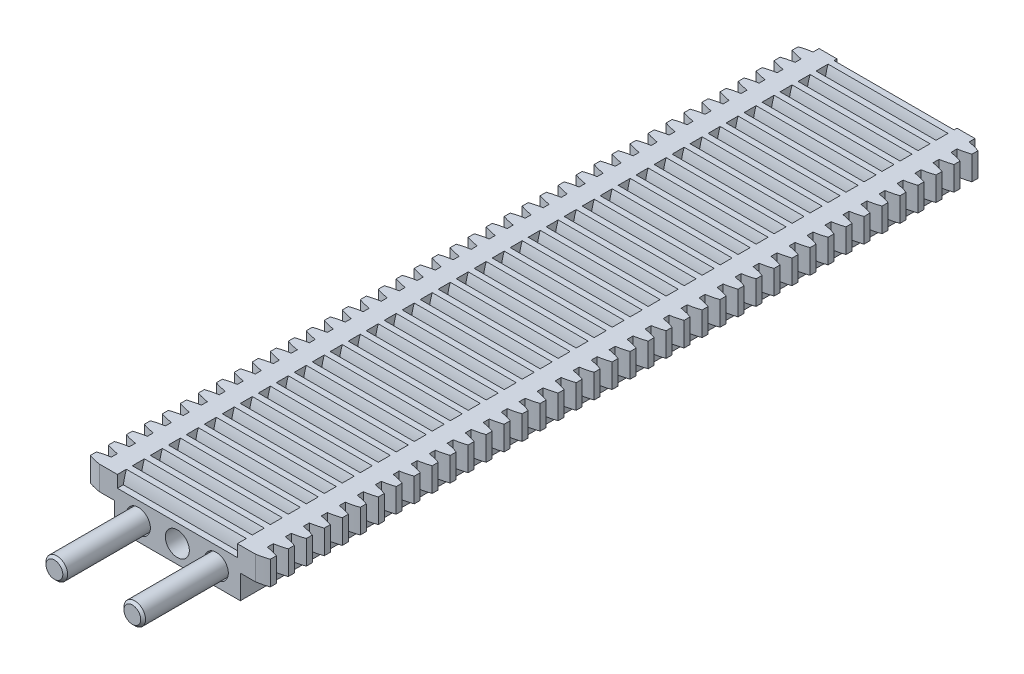
SolidWorks part; units mm, degrees
ref_plane "前视基准面" through (0, 0, 0) normal (0, 0, 1) x (1, 0, 0)
ref_plane "上视基准面" through (0, 0, 0) normal (0, 1, 0) x (1, 0, 0)
ref_plane "右视基准面" through (0, 0, 0) normal (1, 0, 0) x (0, 0, -1)
sketch "草图1" plane through (0, 0, 0) normal (0, 0, 1) x (1, 0, 0)
  line L0 (5.25, 2) -> (6.5, 2)
  line L1 (-5.25, 0) -> (5.25, 0)
  line L2 (-5.25, 0) -> (-5.25, 2)
  line L4 (5.25, 0) -> (5.25, 2)
  line L5 (-6.5, 2) -> (-5.25, 2)
  line L6 (-6.5, 2) -> (-6.5, 4)
  line L7 (-6.5, 4) -> (6.5, 4)
  line L8 (6.5, 2) -> (6.5, 4)
extrude "凸台-拉伸1" add sketch "草图1" against normal blind 60
sketch "草图2" plane through (0, 0, 0) normal (0, 0, 1) x (1, 0, 0)
  line L0 (-1.95, -2.5) -> (-1.1658, -2.5)
  line L1 (-1.95, -2.5) -> (-1.95, -1.5556)
  line L2 (-5.25, 0) -> (5.25, 0) construction
  line L3 (1.95, -2.5) -> (1.95, -1.5556)
  line L4 (0, 0) -> (-1.1658, -2.5)
  line L5 (-1.5, 0) -> (0, 0)
  line L6 (-1.5, 0) -> (-1.5, -0.6771)
  line L7 (0, 0) -> (1.1658, -2.5)
  line L8 (1.5, 0) -> (1.5, -0.6771)
  line L9 (1.1658, -2.5) -> (1.95, -2.5)
  line L10 (0, 0) -> (1.5, 0)
  arc A0 (-1.5, -0.6771) -> (-1.95, -1.5556) centre (0, -2) ccw
  arc A2 (1.95, -1.5556) -> (1.5, -0.6771) centre (0, -2) ccw
  line M2 (-5.25, 0) -> (5.25, 0)
extrude "凸台-拉伸2" add sketch "草图2" against normal blind 54 from offset 3 contours L6 A0 L1 L0 L4 M2 | L3 A2 L8 L7 L9 M2 region at (-1.1423, -1.1553, 0) region at (1.1423, -1.1553, 0) offset against normal yes
sketch "草图3" plane through (0, 0, 0) normal (0, 0, 1) x (1, 0, 0)
  circle A0 centre (-3.25, 1.5) radius 1
  circle A1 centre (0, 1.5) radius 1
  circle A2 centre (3.25, 1.5) radius 1
extrude "切除-拉伸1" cut sketch "草图3" against normal through all
sketch "草图4" plane through (0, 0, 0) normal (0, 0, 1) x (1, 0, 0)
  circle A0 centre (-3.25, 1.5) radius 0.9
  circle A1 centre (3.25, 1.5) radius 0.9
extrude "凸台-拉伸3" add sketch "草图4" along normal blind 7 and the other way blind 7 separate body
fillet "圆角1" radius 0.1 8 edges at (-1.1658, -2.5, -30) (-1.5579, -2.5, -57) (-1.95, -2.5, -30) (-1.5579, -2.5, -3) (1.95, -2.5, -30) (1.5579, -2.5, -57) (1.1658, -2.5, -30) (1.5579, -2.5, -3)
chamfer "倒角2" distance 0.2 angle 45 1 edges at (-2.35, 1.5, 7)
chamfer "倒角3" distance 0.2 angle 45 1 edges at (4.15, 1.5, 7)
sketch "草图6" plane through (0, 4, 0) normal (0, 1, 0) x (1, 0, 0)
  line L0 (-6.5, 59.5) -> (-6.5, 58.5)
  line L1 (-6.5, 60) -> (-6.5, 0) construction
  line L2 (-6.5, 58) -> (-6.5, 57)
  line L3 (-7.5, 59.25) -> (-7.5, 58.75)
  line L4 (-7.5, 57.75) -> (-7.5, 57.25)
  line L5 (-7.5, 56.25) -> (-7.5, 55.75)
  line L6 (-6.5, 56.5) -> (-6.5, 55.5)
  line L7 (-7.5, 54.75) -> (-7.5, 54.25)
  line L8 (-6.5, 55) -> (-6.5, 54)
  line L9 (-7.5, 53.25) -> (-7.5, 52.75)
  line L10 (-6.5, 53.5) -> (-6.5, 52.5)
  line L11 (-7.5, 51.75) -> (-7.5, 51.25)
  line L12 (-6.5, 52) -> (-6.5, 51)
  line L13 (-7.5, 50.25) -> (-7.5, 49.75)
  line L14 (-6.5, 50.5) -> (-6.5, 49.5)
  line L15 (-7.5, 48.75) -> (-7.5, 48.25)
  line L16 (-6.5, 49) -> (-6.5, 48)
  line L17 (-7.5, 47.25) -> (-7.5, 46.75)
  line L18 (-6.5, 47.5) -> (-6.5, 46.5)
  line L19 (-7.5, 45.75) -> (-7.5, 45.25)
  line L20 (-6.5, 46) -> (-6.5, 45)
  line L21 (-7.5, 44.25) -> (-7.5, 43.75)
  line L22 (-6.5, 44.5) -> (-6.5, 43.5)
  line L23 (-7.5, 42.75) -> (-7.5, 42.25)
  line L24 (-6.5, 43) -> (-6.5, 42)
  line L25 (-7.5, 41.25) -> (-7.5, 40.75)
  line L26 (-6.5, 41.5) -> (-6.5, 40.5)
  line L27 (-7.5, 39.75) -> (-7.5, 39.25)
  line L28 (-6.5, 40) -> (-6.5, 39)
  line L29 (-7.5, 38.25) -> (-7.5, 37.75)
  line L30 (-6.5, 38.5) -> (-6.5, 37.5)
  line L31 (-7.5, 36.75) -> (-7.5, 36.25)
  line L32 (-6.5, 37) -> (-6.5, 36)
  line L33 (-7.5, 35.25) -> (-7.5, 34.75)
  line L34 (-6.5, 35.5) -> (-6.5, 34.5)
  line L35 (-7.5, 33.75) -> (-7.5, 33.25)
  line L36 (-6.5, 34) -> (-6.5, 33)
  line L37 (-7.5, 32.25) -> (-7.5, 31.75)
  line L38 (-6.5, 32.5) -> (-6.5, 31.5)
  line L39 (-7.5, 30.75) -> (-7.5, 30.25)
  line L40 (-6.5, 31) -> (-6.5, 30)
  line L41 (-7.5, 29.25) -> (-7.5, 28.75)
  line L42 (-6.5, 29.5) -> (-6.5, 28.5)
  line L43 (-7.5, 27.75) -> (-7.5, 27.25)
  line L44 (-6.5, 28) -> (-6.5, 27)
  line L45 (-7.5, 26.25) -> (-7.5, 25.75)
  line L46 (-6.5, 26.5) -> (-6.5, 25.5)
  line L47 (-7.5, 24.75) -> (-7.5, 24.25)
  line L48 (-6.5, 25) -> (-6.5, 24)
  line L49 (-7.5, 23.25) -> (-7.5, 22.75)
  line L50 (-6.5, 23.5) -> (-6.5, 22.5)
  line L51 (-7.5, 21.75) -> (-7.5, 21.25)
  line L52 (-6.5, 22) -> (-6.5, 21)
  line L53 (-7.5, 20.25) -> (-7.5, 19.75)
  line L54 (-6.5, 20.5) -> (-6.5, 19.5)
  line L55 (-7.5, 18.75) -> (-7.5, 18.25)
  line L56 (-6.5, 19) -> (-6.5, 18)
  line L57 (-7.5, 17.25) -> (-7.5, 16.75)
  line L58 (-6.5, 17.5) -> (-6.5, 16.5)
  line L59 (-7.5, 15.75) -> (-7.5, 15.25)
  line L60 (-6.5, 16) -> (-6.5, 15)
  line L61 (-7.5, 14.25) -> (-7.5, 13.75)
  line L62 (-6.5, 14.5) -> (-6.5, 13.5)
  line L63 (-7.5, 12.75) -> (-7.5, 12.25)
  line L64 (-6.5, 13) -> (-6.5, 12)
  line L65 (-7.5, 11.25) -> (-7.5, 10.75)
  line L66 (-6.5, 11.5) -> (-6.5, 10.5)
  line L67 (-7.5, 9.75) -> (-7.5, 9.25)
  line L68 (-6.5, 10) -> (-6.5, 9)
  line L69 (-7.5, 8.25) -> (-7.5, 7.75)
  line L70 (-6.5, 8.5) -> (-6.5, 7.5)
  line L71 (-7.5, 6.75) -> (-7.5, 6.25)
  line L72 (-6.5, 7) -> (-6.5, 6)
  line L73 (-7.5, 5.25) -> (-7.5, 4.75)
  line L74 (-6.5, 5.5) -> (-6.5, 4.5)
  line L75 (-7.5, 3.75) -> (-7.5, 3.25)
  line L76 (-6.5, 4) -> (-6.5, 3)
  line L77 (-7.5, 2.25) -> (-7.5, 1.75)
  line L78 (-6.5, 2.5) -> (-6.5, 1.5)
  line L79 (-6.5, 1) -> (-6.5, 0)
  line L80 (-7.5, 0.75) -> (-7.5, 0.25)
  line L81 (0, 62.425) -> (0, -2.925) construction
  line L82 (7.5, 0.75) -> (7.5, 0.25)
  line L83 (6.5, 1) -> (6.5, 0)
  line L84 (6.5, 2.5) -> (6.5, 1.5)
  line L85 (7.5, 2.25) -> (7.5, 1.75)
  line L86 (6.5, 4) -> (6.5, 3)
  line L87 (7.5, 3.75) -> (7.5, 3.25)
  line L88 (6.5, 5.5) -> (6.5, 4.5)
  line L89 (7.5, 5.25) -> (7.5, 4.75)
  line L90 (6.5, 7) -> (6.5, 6)
  line L91 (7.5, 6.75) -> (7.5, 6.25)
  line L92 (6.5, 8.5) -> (6.5, 7.5)
  line L93 (7.5, 8.25) -> (7.5, 7.75)
  line L94 (6.5, 10) -> (6.5, 9)
  line L95 (7.5, 9.75) -> (7.5, 9.25)
  line L96 (6.5, 11.5) -> (6.5, 10.5)
  line L97 (7.5, 11.25) -> (7.5, 10.75)
  line L98 (6.5, 13) -> (6.5, 12)
  line L99 (7.5, 12.75) -> (7.5, 12.25)
  line L100 (6.5, 14.5) -> (6.5, 13.5)
  line L101 (7.5, 14.25) -> (7.5, 13.75)
  line L102 (6.5, 16) -> (6.5, 15)
  line L103 (7.5, 15.75) -> (7.5, 15.25)
  line L104 (6.5, 17.5) -> (6.5, 16.5)
  line L105 (7.5, 17.25) -> (7.5, 16.75)
  line L106 (6.5, 19) -> (6.5, 18)
  line L107 (7.5, 18.75) -> (7.5, 18.25)
  line L108 (6.5, 20.5) -> (6.5, 19.5)
  line L109 (7.5, 20.25) -> (7.5, 19.75)
  line L110 (6.5, 22) -> (6.5, 21)
  line L111 (7.5, 21.75) -> (7.5, 21.25)
  line L112 (6.5, 23.5) -> (6.5, 22.5)
  line L113 (7.5, 23.25) -> (7.5, 22.75)
  line L114 (6.5, 25) -> (6.5, 24)
  line L115 (7.5, 24.75) -> (7.5, 24.25)
  line L116 (6.5, 26.5) -> (6.5, 25.5)
  line L117 (7.5, 26.25) -> (7.5, 25.75)
  line L118 (6.5, 28) -> (6.5, 27)
  line L119 (7.5, 27.75) -> (7.5, 27.25)
  line L120 (6.5, 29.5) -> (6.5, 28.5)
  line L121 (7.5, 29.25) -> (7.5, 28.75)
  line L122 (6.5, 31) -> (6.5, 30)
  line L123 (7.5, 30.75) -> (7.5, 30.25)
  line L124 (6.5, 32.5) -> (6.5, 31.5)
  line L125 (7.5, 32.25) -> (7.5, 31.75)
  line L126 (6.5, 34) -> (6.5, 33)
  line L127 (7.5, 33.75) -> (7.5, 33.25)
  line L128 (6.5, 35.5) -> (6.5, 34.5)
  line L129 (7.5, 35.25) -> (7.5, 34.75)
  line L130 (6.5, 37) -> (6.5, 36)
  line L131 (7.5, 36.75) -> (7.5, 36.25)
  line L132 (6.5, 38.5) -> (6.5, 37.5)
  line L133 (7.5, 38.25) -> (7.5, 37.75)
  line L134 (6.5, 40) -> (6.5, 39)
  line L135 (7.5, 39.75) -> (7.5, 39.25)
  line L136 (6.5, 41.5) -> (6.5, 40.5)
  line L137 (7.5, 41.25) -> (7.5, 40.75)
  line L138 (6.5, 43) -> (6.5, 42)
  line L139 (7.5, 42.75) -> (7.5, 42.25)
  line L140 (6.5, 44.5) -> (6.5, 43.5)
  line L141 (7.5, 44.25) -> (7.5, 43.75)
  line L142 (6.5, 46) -> (6.5, 45)
  line L143 (7.5, 45.75) -> (7.5, 45.25)
  line L144 (6.5, 47.5) -> (6.5, 46.5)
  line L145 (7.5, 47.25) -> (7.5, 46.75)
  line L146 (6.5, 49) -> (6.5, 48)
  line L147 (7.5, 48.75) -> (7.5, 48.25)
  line L148 (6.5, 50.5) -> (6.5, 49.5)
  line L149 (7.5, 50.25) -> (7.5, 49.75)
  line L150 (6.5, 52) -> (6.5, 51)
  line L151 (7.5, 51.75) -> (7.5, 51.25)
  line L152 (6.5, 53.5) -> (6.5, 52.5)
  line L153 (7.5, 53.25) -> (7.5, 52.75)
  line L154 (6.5, 55) -> (6.5, 54)
  line L155 (7.5, 54.75) -> (7.5, 54.25)
  line L156 (6.5, 56.5) -> (6.5, 55.5)
  line L157 (7.5, 56.25) -> (7.5, 55.75)
  line L158 (7.5, 57.75) -> (7.5, 57.25)
  line L159 (7.5, 59.25) -> (7.5, 58.75)
  line L160 (6.5, 58) -> (6.5, 57)
  line L161 (6.5, 59.5) -> (6.5, 58.5)
  arc A0 (-7.5, 58.75) -> (-6.5, 58.5) centre (-5.675, 63.925) ccw
  arc A1 (-7.5, 59.25) -> (-6.5, 59.5) centre (-5.675, 54.075) cw
  arc A2 (-7.5, 57.25) -> (-6.5, 57) centre (-5.675, 62.425) ccw
  arc A3 (-7.5, 57.75) -> (-6.5, 58) centre (-5.675, 52.575) cw
  arc A4 (-7.5, 54.25) -> (-6.5, 54) centre (-5.675, 59.425) ccw
  arc A5 (-7.5, 56.25) -> (-6.5, 56.5) centre (-5.675, 51.075) cw
  arc A6 (-7.5, 54.75) -> (-6.5, 55) centre (-5.675, 49.575) cw
  arc A7 (-7.5, 55.75) -> (-6.5, 55.5) centre (-5.675, 60.925) ccw
  arc A8 (-7.5, 51.25) -> (-6.5, 51) centre (-5.675, 56.425) ccw
  arc A9 (-7.5, 53.25) -> (-6.5, 53.5) centre (-5.675, 48.075) cw
  arc A10 (-7.5, 51.75) -> (-6.5, 52) centre (-5.675, 46.575) cw
  arc A11 (-7.5, 52.75) -> (-6.5, 52.5) centre (-5.675, 57.925) ccw
  arc A12 (-7.5, 48.25) -> (-6.5, 48) centre (-5.675, 53.425) ccw
  arc A13 (-7.5, 50.25) -> (-6.5, 50.5) centre (-5.675, 45.075) cw
  arc A14 (-7.5, 48.75) -> (-6.5, 49) centre (-5.675, 43.575) cw
  arc A15 (-7.5, 49.75) -> (-6.5, 49.5) centre (-5.675, 54.925) ccw
  arc A16 (-7.5, 45.25) -> (-6.5, 45) centre (-5.675, 50.425) ccw
  arc A17 (-7.5, 47.25) -> (-6.5, 47.5) centre (-5.675, 42.075) cw
  arc A18 (-7.5, 45.75) -> (-6.5, 46) centre (-5.675, 40.575) cw
  arc A19 (-7.5, 46.75) -> (-6.5, 46.5) centre (-5.675, 51.925) ccw
  arc A20 (-7.5, 42.25) -> (-6.5, 42) centre (-5.675, 47.425) ccw
  arc A21 (-7.5, 44.25) -> (-6.5, 44.5) centre (-5.675, 39.075) cw
  arc A22 (-7.5, 42.75) -> (-6.5, 43) centre (-5.675, 37.575) cw
  arc A23 (-7.5, 43.75) -> (-6.5, 43.5) centre (-5.675, 48.925) ccw
  arc A24 (-7.5, 39.25) -> (-6.5, 39) centre (-5.675, 44.425) ccw
  arc A25 (-7.5, 41.25) -> (-6.5, 41.5) centre (-5.675, 36.075) cw
  arc A26 (-7.5, 39.75) -> (-6.5, 40) centre (-5.675, 34.575) cw
  arc A27 (-7.5, 40.75) -> (-6.5, 40.5) centre (-5.675, 45.925) ccw
  arc A28 (-7.5, 36.25) -> (-6.5, 36) centre (-5.675, 41.425) ccw
  arc A29 (-7.5, 38.25) -> (-6.5, 38.5) centre (-5.675, 33.075) cw
  arc A30 (-7.5, 36.75) -> (-6.5, 37) centre (-5.675, 31.575) cw
  arc A31 (-7.5, 37.75) -> (-6.5, 37.5) centre (-5.675, 42.925) ccw
  arc A32 (-7.5, 33.25) -> (-6.5, 33) centre (-5.675, 38.425) ccw
  arc A33 (-7.5, 35.25) -> (-6.5, 35.5) centre (-5.675, 30.075) cw
  arc A34 (-7.5, 33.75) -> (-6.5, 34) centre (-5.675, 28.575) cw
  arc A35 (-7.5, 34.75) -> (-6.5, 34.5) centre (-5.675, 39.925) ccw
  arc A36 (-7.5, 30.25) -> (-6.5, 30) centre (-5.675, 35.425) ccw
  arc A37 (-7.5, 32.25) -> (-6.5, 32.5) centre (-5.675, 27.075) cw
  arc A38 (-7.5, 30.75) -> (-6.5, 31) centre (-5.675, 25.575) cw
  arc A39 (-7.5, 31.75) -> (-6.5, 31.5) centre (-5.675, 36.925) ccw
  arc A40 (-7.5, 27.25) -> (-6.5, 27) centre (-5.675, 32.425) ccw
  arc A41 (-7.5, 29.25) -> (-6.5, 29.5) centre (-5.675, 24.075) cw
  arc A42 (-7.5, 27.75) -> (-6.5, 28) centre (-5.675, 22.575) cw
  arc A43 (-7.5, 28.75) -> (-6.5, 28.5) centre (-5.675, 33.925) ccw
  arc A44 (-7.5, 24.25) -> (-6.5, 24) centre (-5.675, 29.425) ccw
  arc A45 (-7.5, 26.25) -> (-6.5, 26.5) centre (-5.675, 21.075) cw
  arc A46 (-7.5, 24.75) -> (-6.5, 25) centre (-5.675, 19.575) cw
  arc A47 (-7.5, 25.75) -> (-6.5, 25.5) centre (-5.675, 30.925) ccw
  arc A48 (-7.5, 21.25) -> (-6.5, 21) centre (-5.675, 26.425) ccw
  arc A49 (-7.5, 23.25) -> (-6.5, 23.5) centre (-5.675, 18.075) cw
  arc A50 (-7.5, 21.75) -> (-6.5, 22) centre (-5.675, 16.575) cw
  arc A51 (-7.5, 22.75) -> (-6.5, 22.5) centre (-5.675, 27.925) ccw
  arc A52 (-7.5, 18.25) -> (-6.5, 18) centre (-5.675, 23.425) ccw
  arc A53 (-7.5, 20.25) -> (-6.5, 20.5) centre (-5.675, 15.075) cw
  arc A54 (-7.5, 18.75) -> (-6.5, 19) centre (-5.675, 13.575) cw
  arc A55 (-7.5, 19.75) -> (-6.5, 19.5) centre (-5.675, 24.925) ccw
  arc A56 (-7.5, 15.25) -> (-6.5, 15) centre (-5.675, 20.425) ccw
  arc A57 (-7.5, 17.25) -> (-6.5, 17.5) centre (-5.675, 12.075) cw
  arc A58 (-7.5, 15.75) -> (-6.5, 16) centre (-5.675, 10.575) cw
  arc A59 (-7.5, 16.75) -> (-6.5, 16.5) centre (-5.675, 21.925) ccw
  arc A60 (-7.5, 12.25) -> (-6.5, 12) centre (-5.675, 17.425) ccw
  arc A61 (-7.5, 14.25) -> (-6.5, 14.5) centre (-5.675, 9.075) cw
  arc A62 (-7.5, 12.75) -> (-6.5, 13) centre (-5.675, 7.575) cw
  arc A63 (-7.5, 13.75) -> (-6.5, 13.5) centre (-5.675, 18.925) ccw
  arc A64 (-7.5, 9.25) -> (-6.5, 9) centre (-5.675, 14.425) ccw
  arc A65 (-7.5, 11.25) -> (-6.5, 11.5) centre (-5.675, 6.075) cw
  arc A66 (-7.5, 9.75) -> (-6.5, 10) centre (-5.675, 4.575) cw
  arc A67 (-7.5, 10.75) -> (-6.5, 10.5) centre (-5.675, 15.925) ccw
  arc A68 (-7.5, 6.25) -> (-6.5, 6) centre (-5.675, 11.425) ccw
  arc A69 (-7.5, 8.25) -> (-6.5, 8.5) centre (-5.675, 3.075) cw
  arc A70 (-7.5, 6.75) -> (-6.5, 7) centre (-5.675, 1.575) cw
  arc A71 (-7.5, 7.75) -> (-6.5, 7.5) centre (-5.675, 12.925) ccw
  arc A72 (-7.5, 3.25) -> (-6.5, 3) centre (-5.675, 8.425) ccw
  arc A73 (-7.5, 5.25) -> (-6.5, 5.5) centre (-5.675, 0.075) cw
  arc A74 (-7.5, 3.75) -> (-6.5, 4) centre (-5.675, -1.425) cw
  arc A75 (-7.5, 4.75) -> (-6.5, 4.5) centre (-5.675, 9.925) ccw
  arc A76 (-7.5, 1.75) -> (-6.5, 1.5) centre (-5.675, 6.925) ccw
  arc A77 (-7.5, 2.25) -> (-6.5, 2.5) centre (-5.675, -2.925) cw
  arc A78 (-7.5, 0.25) -> (-6.5, 0) centre (-5.675, 5.425) ccw
  arc A79 (-7.5, 0.75) -> (-6.5, 1) centre (-5.675, -4.425) cw
  arc A80 (7.5, 0.75) -> (6.5, 1) centre (5.675, -4.425) ccw
  arc A81 (7.5, 0.25) -> (6.5, 0) centre (5.675, 5.425) cw
  arc A82 (7.5, 2.25) -> (6.5, 2.5) centre (5.675, -2.925) ccw
  arc A83 (7.5, 1.75) -> (6.5, 1.5) centre (5.675, 6.925) cw
  arc A84 (7.5, 4.75) -> (6.5, 4.5) centre (5.675, 9.925) cw
  arc A85 (7.5, 3.75) -> (6.5, 4) centre (5.675, -1.425) ccw
  arc A86 (7.5, 5.25) -> (6.5, 5.5) centre (5.675, 0.075) ccw
  arc A87 (7.5, 3.25) -> (6.5, 3) centre (5.675, 8.425) cw
  arc A88 (7.5, 7.75) -> (6.5, 7.5) centre (5.675, 12.925) cw
  arc A89 (7.5, 6.75) -> (6.5, 7) centre (5.675, 1.575) ccw
  arc A90 (7.5, 8.25) -> (6.5, 8.5) centre (5.675, 3.075) ccw
  arc A91 (7.5, 6.25) -> (6.5, 6) centre (5.675, 11.425) cw
  arc A92 (7.5, 10.75) -> (6.5, 10.5) centre (5.675, 15.925) cw
  arc A93 (7.5, 9.75) -> (6.5, 10) centre (5.675, 4.575) ccw
  arc A94 (7.5, 11.25) -> (6.5, 11.5) centre (5.675, 6.075) ccw
  arc A95 (7.5, 9.25) -> (6.5, 9) centre (5.675, 14.425) cw
  arc A96 (7.5, 13.75) -> (6.5, 13.5) centre (5.675, 18.925) cw
  arc A97 (7.5, 12.75) -> (6.5, 13) centre (5.675, 7.575) ccw
  arc A98 (7.5, 14.25) -> (6.5, 14.5) centre (5.675, 9.075) ccw
  arc A99 (7.5, 12.25) -> (6.5, 12) centre (5.675, 17.425) cw
  arc A100 (7.5, 16.75) -> (6.5, 16.5) centre (5.675, 21.925) cw
  arc A101 (7.5, 15.75) -> (6.5, 16) centre (5.675, 10.575) ccw
  arc A102 (7.5, 17.25) -> (6.5, 17.5) centre (5.675, 12.075) ccw
  arc A103 (7.5, 15.25) -> (6.5, 15) centre (5.675, 20.425) cw
  arc A104 (7.5, 19.75) -> (6.5, 19.5) centre (5.675, 24.925) cw
  arc A105 (7.5, 18.75) -> (6.5, 19) centre (5.675, 13.575) ccw
  arc A106 (7.5, 20.25) -> (6.5, 20.5) centre (5.675, 15.075) ccw
  arc A107 (7.5, 18.25) -> (6.5, 18) centre (5.675, 23.425) cw
  arc A108 (7.5, 22.75) -> (6.5, 22.5) centre (5.675, 27.925) cw
  arc A109 (7.5, 21.75) -> (6.5, 22) centre (5.675, 16.575) ccw
  arc A110 (7.5, 23.25) -> (6.5, 23.5) centre (5.675, 18.075) ccw
  arc A111 (7.5, 21.25) -> (6.5, 21) centre (5.675, 26.425) cw
  arc A112 (7.5, 25.75) -> (6.5, 25.5) centre (5.675, 30.925) cw
  arc A113 (7.5, 24.75) -> (6.5, 25) centre (5.675, 19.575) ccw
  arc A114 (7.5, 26.25) -> (6.5, 26.5) centre (5.675, 21.075) ccw
  arc A115 (7.5, 24.25) -> (6.5, 24) centre (5.675, 29.425) cw
  arc A116 (7.5, 28.75) -> (6.5, 28.5) centre (5.675, 33.925) cw
  arc A117 (7.5, 27.75) -> (6.5, 28) centre (5.675, 22.575) ccw
  arc A118 (7.5, 29.25) -> (6.5, 29.5) centre (5.675, 24.075) ccw
  arc A119 (7.5, 27.25) -> (6.5, 27) centre (5.675, 32.425) cw
  arc A120 (7.5, 31.75) -> (6.5, 31.5) centre (5.675, 36.925) cw
  arc A121 (7.5, 30.75) -> (6.5, 31) centre (5.675, 25.575) ccw
  arc A122 (7.5, 32.25) -> (6.5, 32.5) centre (5.675, 27.075) ccw
  arc A123 (7.5, 30.25) -> (6.5, 30) centre (5.675, 35.425) cw
  arc A124 (7.5, 34.75) -> (6.5, 34.5) centre (5.675, 39.925) cw
  arc A125 (7.5, 33.75) -> (6.5, 34) centre (5.675, 28.575) ccw
  arc A126 (7.5, 35.25) -> (6.5, 35.5) centre (5.675, 30.075) ccw
  arc A127 (7.5, 33.25) -> (6.5, 33) centre (5.675, 38.425) cw
  arc A128 (7.5, 37.75) -> (6.5, 37.5) centre (5.675, 42.925) cw
  arc A129 (7.5, 36.75) -> (6.5, 37) centre (5.675, 31.575) ccw
  arc A130 (7.5, 38.25) -> (6.5, 38.5) centre (5.675, 33.075) ccw
  arc A131 (7.5, 36.25) -> (6.5, 36) centre (5.675, 41.425) cw
  arc A132 (7.5, 40.75) -> (6.5, 40.5) centre (5.675, 45.925) cw
  arc A133 (7.5, 39.75) -> (6.5, 40) centre (5.675, 34.575) ccw
  arc A134 (7.5, 41.25) -> (6.5, 41.5) centre (5.675, 36.075) ccw
  arc A135 (7.5, 39.25) -> (6.5, 39) centre (5.675, 44.425) cw
  arc A136 (7.5, 43.75) -> (6.5, 43.5) centre (5.675, 48.925) cw
  arc A137 (7.5, 42.75) -> (6.5, 43) centre (5.675, 37.575) ccw
  arc A138 (7.5, 44.25) -> (6.5, 44.5) centre (5.675, 39.075) ccw
  arc A139 (7.5, 42.25) -> (6.5, 42) centre (5.675, 47.425) cw
  arc A140 (7.5, 46.75) -> (6.5, 46.5) centre (5.675, 51.925) cw
  arc A141 (7.5, 45.75) -> (6.5, 46) centre (5.675, 40.575) ccw
  arc A142 (7.5, 47.25) -> (6.5, 47.5) centre (5.675, 42.075) ccw
  arc A143 (7.5, 45.25) -> (6.5, 45) centre (5.675, 50.425) cw
  arc A144 (7.5, 49.75) -> (6.5, 49.5) centre (5.675, 54.925) cw
  arc A145 (7.5, 48.75) -> (6.5, 49) centre (5.675, 43.575) ccw
  arc A146 (7.5, 50.25) -> (6.5, 50.5) centre (5.675, 45.075) ccw
  arc A147 (7.5, 48.25) -> (6.5, 48) centre (5.675, 53.425) cw
  arc A148 (7.5, 52.75) -> (6.5, 52.5) centre (5.675, 57.925) cw
  arc A149 (7.5, 51.75) -> (6.5, 52) centre (5.675, 46.575) ccw
  arc A150 (7.5, 53.25) -> (6.5, 53.5) centre (5.675, 48.075) ccw
  arc A151 (7.5, 51.25) -> (6.5, 51) centre (5.675, 56.425) cw
  arc A152 (7.5, 55.75) -> (6.5, 55.5) centre (5.675, 60.925) cw
  arc A153 (7.5, 54.75) -> (6.5, 55) centre (5.675, 49.575) ccw
  arc A154 (7.5, 56.25) -> (6.5, 56.5) centre (5.675, 51.075) ccw
  arc A155 (7.5, 54.25) -> (6.5, 54) centre (5.675, 59.425) cw
  arc A156 (7.5, 57.75) -> (6.5, 58) centre (5.675, 52.575) ccw
  arc A157 (7.5, 57.25) -> (6.5, 57) centre (5.675, 62.425) cw
  arc A158 (7.5, 59.25) -> (6.5, 59.5) centre (5.675, 54.075) ccw
  arc A159 (7.5, 58.75) -> (6.5, 58.5) centre (5.675, 63.925) cw
extrude "凸台-拉伸4" add sketch "草图6" against normal up to surface (2 mm away) up to face at (-5.875, 2, -30)
sketch "草图7" plane through (0, 0, 0) normal (1, 0, 0) x (0, 0, -1)
  line L0 (2.75, 4) -> (3.75, 4)
  line L1 (1.25, 4) -> (1, 4) construction
  line L2 (3, 3) -> (3.5, 3)
  line L3 (1.5, 4) -> (1, 4) construction
  line L4 (4.25, 4) -> (5.25, 4)
  line L5 (1.5, 3) -> (2, 3)
  line L6 (1, 4) -> (1, 3.5939) construction
  line L7 (4.5, 3) -> (5, 3)
  line L8 (0.5, 3) -> (0, 3)
  line L9 (1.25, 4) -> (2.25, 4)
  line L10 (5.75, 4) -> (6.75, 4)
  line L11 (6, 3) -> (6.5, 3)
  line L12 (9, 3) -> (9.5, 3)
  line L13 (11.75, 4) -> (12.75, 4)
  line L14 (8.75, 4) -> (9.75, 4)
  line L15 (10.25, 4) -> (11.25, 4)
  line L16 (7.25, 4) -> (8.25, 4)
  line L17 (12, 3) -> (12.5, 3)
  line L18 (10.5, 3) -> (11, 3)
  line L19 (7.5, 3) -> (8, 3)
  line L20 (15, 3) -> (15.5, 3)
  line L21 (17.75, 4) -> (18.75, 4)
  line L22 (14.75, 4) -> (15.75, 4)
  line L23 (16.25, 4) -> (17.25, 4)
  line L24 (13.25, 4) -> (14.25, 4)
  line L25 (18, 3) -> (18.5, 3)
  line L26 (16.5, 3) -> (17, 3)
  line L27 (13.5, 3) -> (14, 3)
  line L28 (24, 3) -> (24.5, 3)
  line L29 (20.75, 4) -> (21.75, 4)
  line L30 (19.5, 3) -> (20, 3)
  line L31 (21, 3) -> (21.5, 3)
  line L32 (19.25, 4) -> (20.25, 4)
  line L33 (22.25, 4) -> (23.25, 4)
  line L34 (22.5, 3) -> (23, 3)
  line L35 (23.75, 4) -> (24.75, 4)
  line L36 (30, 3) -> (30.5, 3)
  line L37 (26.75, 4) -> (27.75, 4)
  line L38 (25.5, 3) -> (26, 3)
  line L39 (27, 3) -> (27.5, 3)
  line L40 (25.25, 4) -> (26.25, 4)
  line L41 (28.25, 4) -> (29.25, 4)
  line L42 (28.5, 3) -> (29, 3)
  line L43 (29.75, 4) -> (30.75, 4)
  line L44 (36, 3) -> (36.5, 3)
  line L45 (32.75, 4) -> (33.75, 4)
  line L46 (31.5, 3) -> (32, 3)
  line L47 (33, 3) -> (33.5, 3)
  line L48 (31.25, 4) -> (32.25, 4)
  line L49 (34.25, 4) -> (35.25, 4)
  line L50 (34.5, 3) -> (35, 3)
  line L51 (35.75, 4) -> (36.75, 4)
  line L52 (42, 3) -> (42.5, 3)
  line L53 (38.75, 4) -> (39.75, 4)
  line L54 (37.5, 3) -> (38, 3)
  line L55 (39, 3) -> (39.5, 3)
  line L56 (37.25, 4) -> (38.25, 4)
  line L57 (40.25, 4) -> (41.25, 4)
  line L58 (40.5, 3) -> (41, 3)
  line L59 (41.75, 4) -> (42.75, 4)
  line L60 (48, 3) -> (48.5, 3)
  line L61 (44.75, 4) -> (45.75, 4)
  line L62 (43.5, 3) -> (44, 3)
  line L63 (45, 3) -> (45.5, 3)
  line L64 (43.25, 4) -> (44.25, 4)
  line L65 (46.25, 4) -> (47.25, 4)
  line L66 (46.5, 3) -> (47, 3)
  line L67 (47.75, 4) -> (48.75, 4)
  line L68 (54, 3) -> (54.5, 3)
  line L69 (50.75, 4) -> (51.75, 4)
  line L70 (49.5, 3) -> (50, 3)
  line L71 (51, 3) -> (51.5, 3)
  line L72 (49.25, 4) -> (50.25, 4)
  line L73 (52.25, 4) -> (53.25, 4)
  line L74 (52.5, 3) -> (53, 3)
  line L75 (53.75, 4) -> (54.75, 4)
  line L76 (0.75, 4) -> (-0.25, 4)
  line L77 (56.75, 4) -> (57.75, 4)
  line L78 (55.5, 3) -> (56, 3)
  line L79 (57, 3) -> (57.5, 3)
  line L80 (55.25, 4) -> (56.25, 4)
  line L81 (58.25, 4) -> (59.25, 4)
  line L82 (58.5, 3) -> (59, 3)
  line L83 (59.25, 4) -> (59.5, 4) construction
  line L84 (60, 4) -> (59.5, 4) construction
  line L85 (59.5, 4) -> (59.5, 3.5184) construction
  line L86 (60.5, 3) -> (60, 3)
  line L87 (60.75, 4) -> (59.75, 4)
  arc A0 (2.25, 4) -> (2, 3) centre (7.425, 2.175) ccw
  arc A1 (1.25, 4) -> (1.5, 3) centre (-3.925, 2.175) cw
  arc A2 (2.75, 4) -> (3, 3) centre (-2.425, 2.175) cw
  arc A3 (3.75, 4) -> (3.5, 3) centre (8.925, 2.175) ccw
  arc A4 (4.25, 4) -> (4.5, 3) centre (-0.925, 2.175) cw
  arc A5 (5.25, 4) -> (5, 3) centre (10.425, 2.175) ccw
  arc A6 (5.75, 4) -> (6, 3) centre (0.575, 2.175) cw
  arc A7 (6.75, 4) -> (6.5, 3) centre (11.925, 2.175) ccw
  arc A8 (11.25, 4) -> (11, 3) centre (16.425, 2.175) ccw
  arc A9 (8.75, 4) -> (9, 3) centre (3.575, 2.175) cw
  arc A10 (12.75, 4) -> (12.5, 3) centre (17.925, 2.175) ccw
  arc A11 (7.25, 4) -> (7.5, 3) centre (2.075, 2.175) cw
  arc A12 (10.25, 4) -> (10.5, 3) centre (5.075, 2.175) cw
  arc A13 (9.75, 4) -> (9.5, 3) centre (14.925, 2.175) ccw
  arc A14 (11.75, 4) -> (12, 3) centre (6.575, 2.175) cw
  arc A15 (8.25, 4) -> (8, 3) centre (13.425, 2.175) ccw
  arc A16 (17.25, 4) -> (17, 3) centre (22.425, 2.175) ccw
  arc A17 (14.75, 4) -> (15, 3) centre (9.575, 2.175) cw
  arc A18 (18.75, 4) -> (18.5, 3) centre (23.925, 2.175) ccw
  arc A19 (13.25, 4) -> (13.5, 3) centre (8.075, 2.175) cw
  arc A20 (16.25, 4) -> (16.5, 3) centre (11.075, 2.175) cw
  arc A21 (15.75, 4) -> (15.5, 3) centre (20.925, 2.175) ccw
  arc A22 (17.75, 4) -> (18, 3) centre (12.575, 2.175) cw
  arc A23 (14.25, 4) -> (14, 3) centre (19.425, 2.175) ccw
  arc A24 (23.25, 4) -> (23, 3) centre (28.425, 2.175) ccw
  arc A25 (24.75, 4) -> (24.5, 3) centre (29.925, 2.175) ccw
  arc A26 (20.25, 4) -> (20, 3) centre (25.425, 2.175) ccw
  arc A27 (21.75, 4) -> (21.5, 3) centre (26.925, 2.175) ccw
  arc A28 (20.75, 4) -> (21, 3) centre (15.575, 2.175) cw
  arc A29 (22.25, 4) -> (22.5, 3) centre (17.075, 2.175) cw
  arc A30 (19.25, 4) -> (19.5, 3) centre (14.075, 2.175) cw
  arc A31 (23.75, 4) -> (24, 3) centre (18.575, 2.175) cw
  arc A32 (29.25, 4) -> (29, 3) centre (34.425, 2.175) ccw
  arc A33 (30.75, 4) -> (30.5, 3) centre (35.925, 2.175) ccw
  arc A34 (26.25, 4) -> (26, 3) centre (31.425, 2.175) ccw
  arc A35 (27.75, 4) -> (27.5, 3) centre (32.925, 2.175) ccw
  arc A36 (26.75, 4) -> (27, 3) centre (21.575, 2.175) cw
  arc A37 (28.25, 4) -> (28.5, 3) centre (23.075, 2.175) cw
  arc A38 (25.25, 4) -> (25.5, 3) centre (20.075, 2.175) cw
  arc A39 (29.75, 4) -> (30, 3) centre (24.575, 2.175) cw
  arc A40 (35.25, 4) -> (35, 3) centre (40.425, 2.175) ccw
  arc A41 (36.75, 4) -> (36.5, 3) centre (41.925, 2.175) ccw
  arc A42 (32.25, 4) -> (32, 3) centre (37.425, 2.175) ccw
  arc A43 (33.75, 4) -> (33.5, 3) centre (38.925, 2.175) ccw
  arc A44 (32.75, 4) -> (33, 3) centre (27.575, 2.175) cw
  arc A45 (34.25, 4) -> (34.5, 3) centre (29.075, 2.175) cw
  arc A46 (31.25, 4) -> (31.5, 3) centre (26.075, 2.175) cw
  arc A47 (35.75, 4) -> (36, 3) centre (30.575, 2.175) cw
  arc A48 (41.25, 4) -> (41, 3) centre (46.425, 2.175) ccw
  arc A49 (42.75, 4) -> (42.5, 3) centre (47.925, 2.175) ccw
  arc A50 (38.25, 4) -> (38, 3) centre (43.425, 2.175) ccw
  arc A51 (39.75, 4) -> (39.5, 3) centre (44.925, 2.175) ccw
  arc A52 (38.75, 4) -> (39, 3) centre (33.575, 2.175) cw
  arc A53 (40.25, 4) -> (40.5, 3) centre (35.075, 2.175) cw
  arc A54 (37.25, 4) -> (37.5, 3) centre (32.075, 2.175) cw
  arc A55 (41.75, 4) -> (42, 3) centre (36.575, 2.175) cw
  arc A56 (47.25, 4) -> (47, 3) centre (52.425, 2.175) ccw
  arc A57 (48.75, 4) -> (48.5, 3) centre (53.925, 2.175) ccw
  arc A58 (44.25, 4) -> (44, 3) centre (49.425, 2.175) ccw
  arc A59 (45.75, 4) -> (45.5, 3) centre (50.925, 2.175) ccw
  arc A60 (44.75, 4) -> (45, 3) centre (39.575, 2.175) cw
  arc A61 (46.25, 4) -> (46.5, 3) centre (41.075, 2.175) cw
  arc A62 (43.25, 4) -> (43.5, 3) centre (38.075, 2.175) cw
  arc A63 (47.75, 4) -> (48, 3) centre (42.575, 2.175) cw
  arc A64 (53.25, 4) -> (53, 3) centre (58.425, 2.175) ccw
  arc A65 (54.75, 4) -> (54.5, 3) centre (59.925, 2.175) ccw
  arc A66 (50.25, 4) -> (50, 3) centre (55.425, 2.175) ccw
  arc A67 (51.75, 4) -> (51.5, 3) centre (56.925, 2.175) ccw
  arc A68 (50.75, 4) -> (51, 3) centre (45.575, 2.175) cw
  arc A69 (52.25, 4) -> (52.5, 3) centre (47.075, 2.175) cw
  arc A70 (49.25, 4) -> (49.5, 3) centre (44.075, 2.175) cw
  arc A71 (53.75, 4) -> (54, 3) centre (48.575, 2.175) cw
  arc A72 (59.25, 4) -> (59, 3) centre (64.425, 2.175) ccw
  arc A73 (-0.25, 4) -> (0, 3) centre (-5.425, 2.175) cw
  arc A74 (56.25, 4) -> (56, 3) centre (61.425, 2.175) ccw
  arc A75 (57.75, 4) -> (57.5, 3) centre (62.925, 2.175) ccw
  arc A76 (56.75, 4) -> (57, 3) centre (51.575, 2.175) cw
  arc A77 (58.25, 4) -> (58.5, 3) centre (53.075, 2.175) cw
  arc A78 (55.25, 4) -> (55.5, 3) centre (50.075, 2.175) cw
  arc A79 (0.75, 4) -> (0.5, 3) centre (5.925, 2.175) ccw
  arc A80 (59.75, 4) -> (60, 3) centre (54.575, 2.175) cw
  arc A81 (60.75, 4) -> (60.5, 3) centre (65.925, 2.175) ccw
  dimension "D1" = 0.25
  dimension "D2" = 0.25
extrude "切除-拉伸2" cut sketch "草图7" against normal blind 5
extrude "切除-拉伸3" cut sketch "草图7<2>" along normal blind 5
sketch "草图7<2>" plane through (0, 0, 0) normal (1, 0, 0) x (0, 0, -1) same geometry as "草图7"
